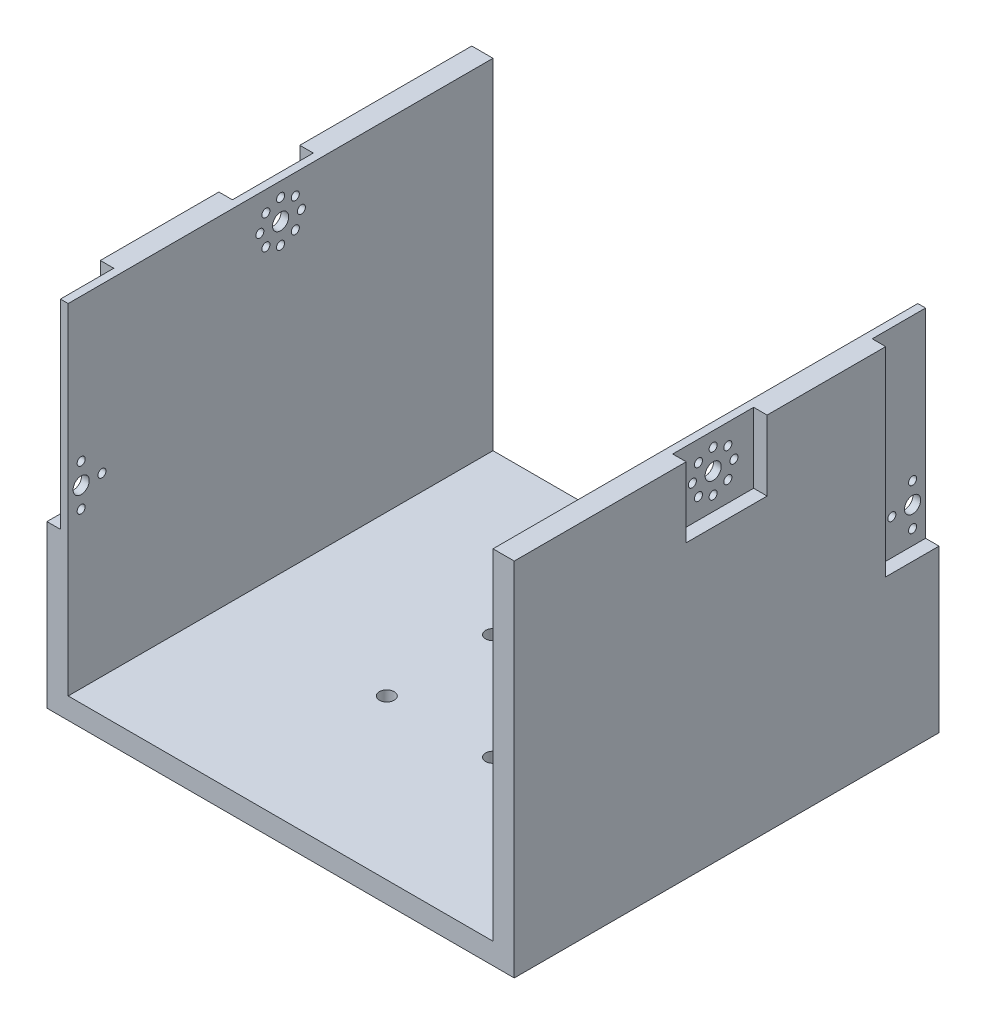
SolidWorks part; units mm, degrees
ref_plane "Front" through (0, 0, 0) normal (0, 0, 1) x (1, 0, 0)
ref_plane "Top" through (0, 0, 0) normal (0, 1, 0) x (1, 0, 0)
ref_plane "Right" through (0, 0, 0) normal (1, 0, 0) x (0, 0, -1)
sketch "Sketch2" plane through (0, 0, 0) normal (0, 1, 0) x (1, 0, 0)
  line L0 (0, 0) -> (0, -100) construction
  line L1 (-100, -100) -> (100, -100)
  line L2 (-100, -100) -> (-100, 100)
  line L3 (-100, 100) -> (100, 100)
  line L4 (100, -100) -> (100, 100)
  line L5 (0, 0) -> (-100, 0) construction
  point P0 (0, 0)
  dimension "D1" = 200
  dimension "D2" = 200
extrude "Boss-Extrude1" add sketch "Sketch2" along normal blind 10
sketch "Sketch3" plane through (0, 0, 0) normal (0, 1, 0) x (1, 0, 0)
  line L0 (-100, -100) -> (100, -100) construction
  line L1 (-100, 100) -> (-110, 100)
  line L2 (-100, 100) -> (-100, -100)
  line L3 (-100, -100) -> (-110, -100)
  line L4 (-110, 100) -> (-110, -100)
  line L5 (0, 0) -> (0, 100) construction
  line L6 (100, 100) -> (-100, 100) construction
  line L7 (110, 100) -> (110, -100)
  line L8 (100, -100) -> (110, -100)
  line L9 (100, 100) -> (100, -100)
  line L10 (100, 100) -> (110, 100)
  dimension "D1" = 10
extrude "Boss-Extrude2" add sketch "Sketch3" along normal blind 170
sketch "Sketch4" plane through (0, 10, 0) normal (0, 1, 0) x (1, 0, 0)
  point P4 (0, 0)
hole_wizard "M6 Clearance Hole1" positions "Sketch5" profile "Sketch6" hole size "M6" standard "ANSI Metric" end condition up to next
sketch "Sketch5" plane through (0, 10, 0) normal (0, 1, 0) x (1, 0, 0)
  line L0 (0, 0) -> (0, 25) construction
  line L1 (0, 25) -> (-25, 25) construction
  line L3 (0, 25) -> (25, 25) construction
  point P0 (-25, 25)
  point P13 (25, 25)
  point P14 (25, -25)
  point P15 (-25, -25)
  dimension "D1" = 25
  dimension "D2" = 4
sketch "Sketch6" plane through (-25, 10, -25) normal (1, 0, 0) x (0, 0, 1)
  line L0 (0, 0) -> (0, 10)
  line L1 (0, 10) -> (3.5, 10)
  line L2 (3.5, 10) -> (3.5, 0)
  line L5 (3.5, 0) -> (0, 0)
  line L11 (0, -6.35) -> (0, 107.95) construction
  dimension "Thru Hole Dia." = 7
  dimension "Thru Hole Depth" = 10
sketch "Sketch7" plane through (100, 0, 0) normal (-1, 0, 0) x (0, 0, 1)
  line L0 (-100, 170) -> (100, 170) construction
  line L1 (0, 153.49) -> (0, 163.269) construction
  line L2 (0, 153.49) -> (0, 163.269) construction
  circle A0 centre (0, 153.49) radius 3.81
  circle A1 centre (0, 163.269) radius 1.8987
  circle A2 centre (6.9148, 160.4048) radius 1.8987
  circle A3 centre (9.779, 153.49) radius 1.8987
  circle A4 centre (6.9148, 146.5752) radius 1.8987
  circle A5 centre (0, 143.711) radius 1.8987
  circle A6 centre (-6.9148, 146.5752) radius 1.8987
  circle A7 centre (-9.779, 153.49) radius 1.8987
  circle A8 centre (-6.9148, 160.4048) radius 1.8987
  point P7 (0, 170)
  dimension "D1" = 7.62
  dimension "D3" = 3.7973
  dimension "D2" = 16.51
  dimension "D6" = 9.779
  dimension "D5" = 8
extrude "Cut-Extrude1" cut sketch "Sketch7" against normal through all both and the other way through all
sketch "Sketch8" plane through (0, 170, 0) normal (0, 1, 0) x (1, 0, 0)
  line L1 (103.65, -19.05) -> (110, -19.05)
  line L2 (103.65, -19.05) -> (103.65, 19.05)
  line L3 (103.65, 19.05) -> (110, 19.05)
  line L4 (110, -19.05) -> (110, 19.05)
  line L5 (103.65, -19.05) -> (110, 19.05) construction
  line L6 (103.65, 19.05) -> (110, -19.05) construction
  line L9 (110, -100) -> (110, 100) construction
  line L10 (0, 0) -> (0, 100) construction
  line L11 (100, 100) -> (-100, 100) construction
  line L13 (-103.65, 19.05) -> (-110, -19.05) construction
  line L14 (-103.65, -19.05) -> (-110, 19.05) construction
  line L16 (-110, -19.05) -> (-110, 19.05)
  line L17 (-103.65, 19.05) -> (-110, 19.05)
  line L18 (-103.65, -19.05) -> (-103.65, 19.05)
  line L19 (-103.65, -19.05) -> (-110, -19.05)
  point P0 (106.825, 0)
  point P12 (110, 0)
  point P23 (-106.825, 0)
  dimension "D1" = 38.1
  dimension "D2" = 6.35
extrude "Cut-Extrude2" cut sketch "Sketch8" against normal blind 33.02
sketch "Sketch9" plane through (110, 0, 0) normal (1, 0, 0) x (0, 0, -1)
  line L0 (77.3824, 76.1083) -> (83.4784, 76.1083) construction
  line L2 (112.9024, 109.6463) -> (112.9024, 76.0983)
  line L3 (112.9024, 76.0983) -> (74.8824, 76.0983)
  line L4 (74.8824, 109.6463) -> (74.8824, 76.0983)
  line L5 (112.9024, 109.6463) -> (74.8824, 76.0983) construction
  line L6 (112.9024, 76.0983) -> (74.8824, 109.6463) construction
  line L7 (77.3824, 85.2523) -> (77.3824, 76.1083) construction
  line L13 (112.9024, 109.6463) -> (112.9024, 170)
  line L14 (19.05, 170) -> (100, 170) construction
  line L15 (112.9024, 170) -> (74.8824, 170)
  line L16 (74.8824, 170) -> (74.8824, 109.6463)
  point P0 (93.8924, 92.8723)
  point P10 (93.8924, 102.6513)
  point P11 (84.1134, 92.8723)
  point P13 (93.8924, 83.0933)
  point P15 (103.6714, 92.8723)
  dimension "D1" = 0.01
  dimension "D2" = 2.5
extrude "Cut-Extrude3" cut sketch "Sketch9" against normal blind 6.35
sketch "Sketch11" plane through (103.65, 0, 0) normal (1, 0, 0) x (0, 0, -1)
  circle A0 centre (93.8924, 92.8723) radius 3.81
  circle A1 centre (0, 153.49) radius 3.81 construction
extrude "Cut-Extrude4" cut sketch "Sketch11" against normal up to next
hole_wizard "#6 Clearance Hole1" positions "Sketch12" profile "Sketch13" hole size "#6" standard "ANSI Inch" end condition up to next
sketch "Sketch12" plane through (103.65, 0, 0) normal (1, 0, 0) x (0, 0, -1)
  point P0 (93.8924, 102.6513)
  point P3 (84.1134, 92.8723)
  point P6 (103.6714, 92.8723)
  point P10 (93.8924, 83.0933)
sketch "Sketch13" plane through (103.65, 102.6513, -93.8924) normal (0, 1, 0) x (0, 0, -1)
  line L0 (0, 0) -> (0, 3.65)
  line L1 (0, 3.65) -> (1.8986, 3.65)
  line L2 (1.8986, 3.65) -> (1.8986, 0)
  line L5 (1.8986, 0) -> (0, 0)
  line L11 (0, -6.35) -> (0, 107.95) construction
  dimension "Thru Hole Dia." = 3.7973
  dimension "Thru Hole Depth" = 3.65
ref_plane "Plane1" through (0, 0, 0) normal (-0.7071, 0, 0.7071) x (0.7071, 0, 0.7071)
ref_axis "Axis1" through (0, 0, 0) along (0, 1, 0)
pattern_circular "CirPattern1" count 2 over 360 about axis through (0, 0, 0) along (0, 1, 0) of "Cut-Extrude3", "Cut-Extrude4", "#6 Clearance Hole1"
equation "\"Longueur\"= 200"
equation "\"D2@Sketch2\"=\"Longueur\""
equation "\"Largeur\"=200"
equation "\"D1@Sketch2\"=\"Largeur\""
